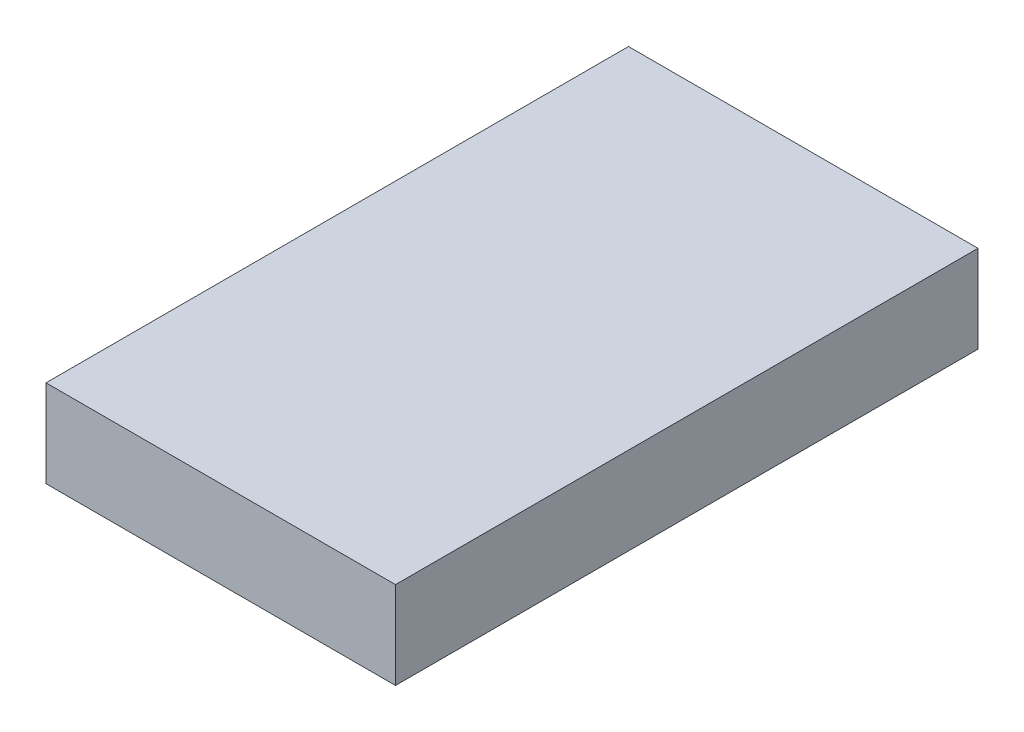
SolidWorks part; units mm, degrees
material "Cast Alloy Steel"
ref_plane "Front Plane" through (0, 0, 0) normal (1, 0, 0) x (0, 1, 0)
ref_plane "Top Plane" through (0, 0, 0) normal (0, 0, 1) x (0, 1, 0)
ref_plane "Right Plane" through (0, 0, 0) normal (0, 1, 0) x (-1, 0, 0)
sketch "Sketch1" plane through (0, 0, 0) normal (1, 0, 0) x (0, 1, 0)
  line L1 (0, -55) -> (0, 55) construction
  line L2 (-450, 150) -> (0, 150)
  line L3 (-450, 150) -> (-450, 0)
  line L4 (-450, 0) -> (0, 0)
  line L5 (0, 150) -> (0, 0)
  line L6 (0, 150) -> (150, 150)
  line L7 (0, 150) -> (0, 1150)
  line L8 (0, 1150) -> (150, 1150)
  line L9 (150, 150) -> (150, 1150)
  line L10 (-450, 0) -> (-600, 0)
  line L11 (-450, 0) -> (-450, -500)
  line L12 (-450, -500) -> (-600, -500)
  line L13 (-600, 0) -> (-600, -500)
  line L14 (55, 0) -> (-55, 0) construction
  dimension "D1" = 1000
  dimension "D2" = 150
  dimension "D3" = 150
  dimension "D4" = 150
  dimension "D5" = 450
  dimension "D6" = 500
  dimension "D7" = 0
  dimension "D8" = 0
extrude "Boss-Extrude2" add sketch "Sketch1" along normal blind 300 and the other way blind 300 contours L6 L9 L8 L7 | L7 L6 L9 L8 region at (0, 75, 650)
